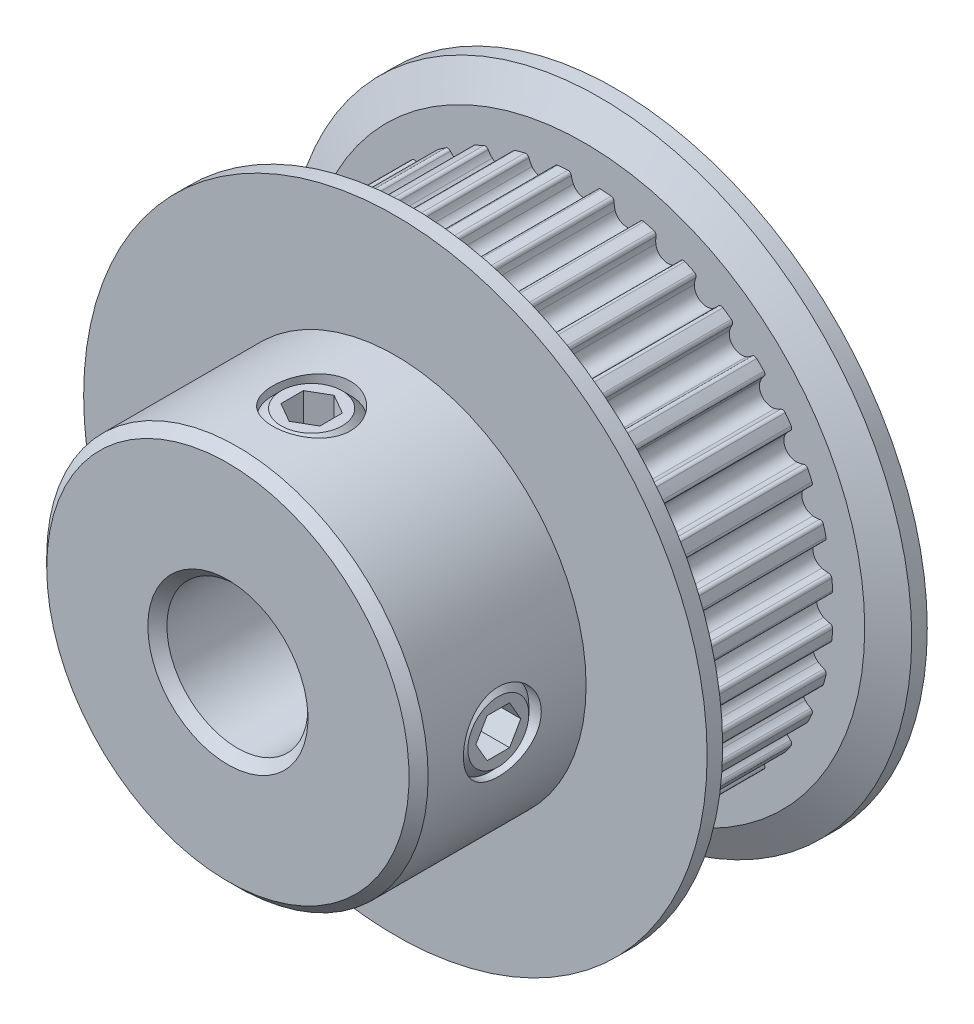
SolidWorks part; units mm, degrees
ref_plane "Front Plane" through (0, 0, 0) normal (0, 0, 1) x (1, 0, 0)
ref_plane "Top Plane" through (0, 0, 0) normal (0, 1, 0) x (1, 0, 0)
ref_plane "Right Plane" through (0, 0, 0) normal (1, 0, 0) x (0, 0, -1)
sketch "Sketch1" plane through (0, 0, 0) normal (0, 0, 1) x (1, 0, 0)
  line L1 (-1.8459, 10.4515) -> (1.8459, 10.4515) construction
  line L4 (0, 0) -> (0, 10.4515) construction
  line L5 (0, 10.4515) -> (0, 14.611) construction
  line L6 (0, 11.4555) -> (1.9924, 11.2809) construction
  line L7 (1.9924, 11.2809) -> (2.8218, 11.1344) construction
  line L8 (1.9924, 11.2809) -> (1.8459, 10.4515) construction
  line L9 (-1.9924, 11.2809) -> (-1.8459, 10.4515) construction
  line L10 (-1.9482, 11.0308) -> (-2.4785, 14.0335)
  line L11 (-2.4785, 14.0335) -> (2.4785, 14.0335)
  line L12 (2.4785, 14.0335) -> (1.9482, 11.0308)
  circle A0 centre (0, 0) radius 11.4555 construction
  circle A1 centre (0, 0) radius 14.0335 construction
  circle A2 centre (0, 0) radius 11.2015 construction
  arc A3 (-0.4989, 10.7633) -> (0.4989, 10.7633) centre (0, 11.0065) ccw
  arc A4 (-0.4989, 10.7633) -> (-0.5884, 11.0497) centre (0.4, 11.2015) cw
  arc A5 (-1.9482, 11.0308) -> (-0.7467, 11.1766) centre (0, 0) cw
  arc A6 (-0.5884, 11.0497) -> (-0.7467, 11.1766) centre (-0.7367, 11.0269) ccw
  arc A7 (1.9482, 11.0308) -> (0.7467, 11.1766) centre (0, 0) ccw
  arc A8 (0.5884, 11.0497) -> (0.7467, 11.1766) centre (0.7367, 11.0269) cw
  arc A9 (0.4989, 10.7633) -> (0.5884, 11.0497) centre (-0.4, 11.2015) ccw
  point P6 (0, 20.9083)
  point P11 (0, 11.4555)
  point P13 (0, 14.0335)
  point P14 (0, 11.2015)
  dimension "D1" = 6.2973
  dimension "D2" = 3.1555
sketch "Sketch2" plane through (0, 0, 0) normal (1, 0, 0) x (0, 0, -1)
  line L0 (-8.7249, 3.175) -> (8.7249, 3.175)
  line L1 (-8.7249, 3.175) -> (-8.7249, 8.585)
  line L2 (-8.7249, 8.585) -> (-1.1851, 8.585)
  line L3 (-1.1851, 8.585) -> (-1.1851, 14.0335)
  line L4 (-1.1851, 14.0335) -> (0.2149, 14.0335) construction
  line L5 (0.2149, 14.0335) -> (0.2149, 11.2015) construction
  line L6 (0.2149, 11.2015) -> (7.3249, 11.2015)
  line L7 (7.3249, 11.2015) -> (7.3249, 14.0335) construction
  line L8 (7.3249, 14.0335) -> (8.7249, 14.0335) construction
  line L9 (8.7249, 14.0335) -> (8.7249, 3.175)
  line L10 (-8.7249, 0) -> (8.7249, 0) construction
  line L11 (8.0249, 14.0335) -> (7.3249, 12.6175)
  line L12 (0.2149, 12.6175) -> (-0.4851, 14.0335)
  line L13 (-1.1851, 14.0335) -> (-0.4851, 14.0335)
  line L14 (0.2149, 12.6175) -> (0.2149, 11.2015)
  line L15 (7.3249, 11.2015) -> (7.3249, 12.6175)
  line L16 (8.0249, 14.0335) -> (8.7249, 14.0335)
  arc A0 (0.2149, 12.6175) -> (-0.4851, 14.0335) centre (-1.5673, 12.6175) ccw construction
  arc A1 (7.3249, 12.6175) -> (8.0249, 14.0335) centre (9.1071, 12.6175) cw construction
  point P12 (0.2149, 12.6175)
  point P14 (-0.4851, 14.0335)
  point P20 (7.3249, 12.6175)
  point P21 (8.0249, 14.0335)
  point P25 (7.3249, 0)
  point P26 (0.2149, 0)
revolve "Revolve1" add sketch "Sketch2" angle 360 mid plane about L10
sketch "Sketch3" plane through (0, 0, 0) normal (0, 0, 1) x (1, 0, 0)
  line L6 (2.4785, 14.0335) -> (-2.4785, 14.0335)
  line L7 (1.9482, 11.0308) -> (2.4785, 14.0335)
  line L8 (-2.4785, 14.0335) -> (-1.9482, 11.0308)
  line L9 (2.4785, 14.0335) -> (-2.4785, 14.0335)
  line L10 (1.9482, 11.0308) -> (2.4785, 14.0335)
  line L11 (-2.4785, 14.0335) -> (-1.9482, 11.0308)
  arc A8 (1.9482, 11.0308) -> (0.7467, 11.1766) centre (0, 0) ccw
  arc A9 (0.7467, 11.1766) -> (0.5884, 11.0497) centre (0.7367, 11.0269) ccw
  arc A10 (0.4989, 10.7633) -> (0.5884, 11.0497) centre (-0.4, 11.2015) ccw
  arc A11 (-0.4989, 10.7633) -> (0.4989, 10.7633) centre (0, 11.0065) ccw
  arc A12 (-0.5884, 11.0497) -> (-0.4989, 10.7633) centre (0.4, 11.2015) ccw
  arc A13 (-0.5884, 11.0497) -> (-0.7467, 11.1766) centre (-0.7367, 11.0269) ccw
  arc A14 (-0.7467, 11.1766) -> (-1.9482, 11.0308) centre (0, 0) ccw
  arc A15 (1.9482, 11.0308) -> (0.7467, 11.1766) centre (0, 0) ccw
  arc A16 (0.7467, 11.1766) -> (0.5884, 11.0497) centre (0.7367, 11.0269) ccw
  arc A17 (0.4989, 10.7633) -> (0.5884, 11.0497) centre (-0.4, 11.2015) ccw
  arc A18 (-0.4989, 10.7633) -> (0.4989, 10.7633) centre (0, 11.0065) ccw
  arc A19 (-0.5884, 11.0497) -> (-0.4989, 10.7633) centre (0.4, 11.2015) ccw
  arc A20 (-0.5884, 11.0497) -> (-0.7467, 11.1766) centre (-0.7367, 11.0269) ccw
  arc A21 (-0.7467, 11.1766) -> (-1.9482, 11.0308) centre (0, 0) ccw
  dimension "D1" = 0
extrude "Cut-Extrude1" cut sketch "Sketch3" against normal up to vertex (7.3249 mm away) from vertex up to point (0, 11.2015, -7.3249) starting at point (0, 11.2015, -0.2149)
pattern_circular "CirPattern1" count 36 over 360 about axis through (0, 0, 8.7249) along (0, 0, 1) of "Cut-Extrude1"
sketch "Sketch4" plane through (0, 0, 0) normal (1, 0, 0) x (0, -1, 0)
  line L0 (0, -1.1851) -> (0, -8.7249) construction
  line L1 (-8.585, -1.1851) -> (8.585, -1.1851) construction
  line L2 (-8.585, -8.7249) -> (8.585, -8.7249) construction
  circle A0 centre (0, -4.955) radius 1.7526
extrude "Cut-Extrude2" cut sketch "Sketch4" along normal through all
ref_plane "Plane1" through (0, 0, 4.955) normal (0, 0, 1) x (1, 0, 0)
sketch "Sketch5" plane through (0, 0, 4.955) normal (0, 0, 1) x (1, 0, 0)
  line L0 (0, 0.1664) -> (0, 8.585) construction
  line L1 (3.175, -1.3716) -> (3.175, 0)
  line L2 (3.556, -1.7526) -> (8.0232, -1.7526)
  line L3 (3.175, 0) -> (8.585, 0) construction
  line L4 (3.175, 0) -> (8.4042, 0)
  line L5 (8.4042, 0) -> (8.4042, -1.3716)
  line L6 (3.556, -1.7526) -> (3.175, -1.3716)
  line L7 (8.4042, -1.3716) -> (8.0232, -1.7526)
  circle A0 centre (0, 0) radius 8.585 construction
  circle A1 centre (0, 0) radius 3.175 construction
  point P2 (3.175, -1.7526)
  point P11 (8.4042, -1.7526)
revolve "Revolve2" add sketch "Sketch5" angle 360 mid plane about L4
sketch "Sketch6" plane through (8.4042, 5.3841, 0) normal (-1, 0, 0) x (0, -1, 0)
  line L1 (5.3841, 5.9669) -> (4.5078, 5.4609)
  line L2 (4.5078, 5.4609) -> (4.5078, 4.4491)
  line L3 (4.5078, 4.4491) -> (5.3841, 3.9431)
  line L4 (5.3841, 3.9431) -> (6.2604, 4.4491)
  line L5 (6.2604, 4.4491) -> (6.2604, 5.4609)
  line L6 (6.2604, 5.4609) -> (5.3841, 5.9669)
  circle A0 centre (5.3841, 4.955) radius 0.8763 construction
  dimension "D1" = 1.7526
extrude "Cut-Extrude3" cut sketch "Sketch6" along normal blind 1.3144
pattern_circular "CirPattern2" count 2 over 90 about axis through (0, 0, 8.7249) along (0, 0, 1) of "Cut-Extrude2", "Revolve2", "Cut-Extrude3"
chamfer "Chamfer1" distance 0.4293 angle 45 2 edges at (3.175, 0, 8.7249) (8.585, 0, 8.7249)
ref_axis "Center Axis 1" through (0, 0, -8.7249) along (0, 0, 1)
ref_plane "Contact Plane 1" through (0, 0, 8.7249) normal (0, 0, 1) x (1, 0, 0)
ref_plane "Contact Plane 2" through (0, 0, -8.7249) normal (0, 0, -1) x (-1, 0, 0)
equation "\"D2@Sketch1\" = \"D1@Sketch1\"/2"
equation "\"D1@Sketch6\" = \"Set Screw@Sketch4\" / 2"
equation "\"D1@Cut-Extrude3\" = \"D1@Sketch6\"*.75"
equation "\"D1@Chamfer1\"=\"Hub Dia@Sketch2\"*.025"
